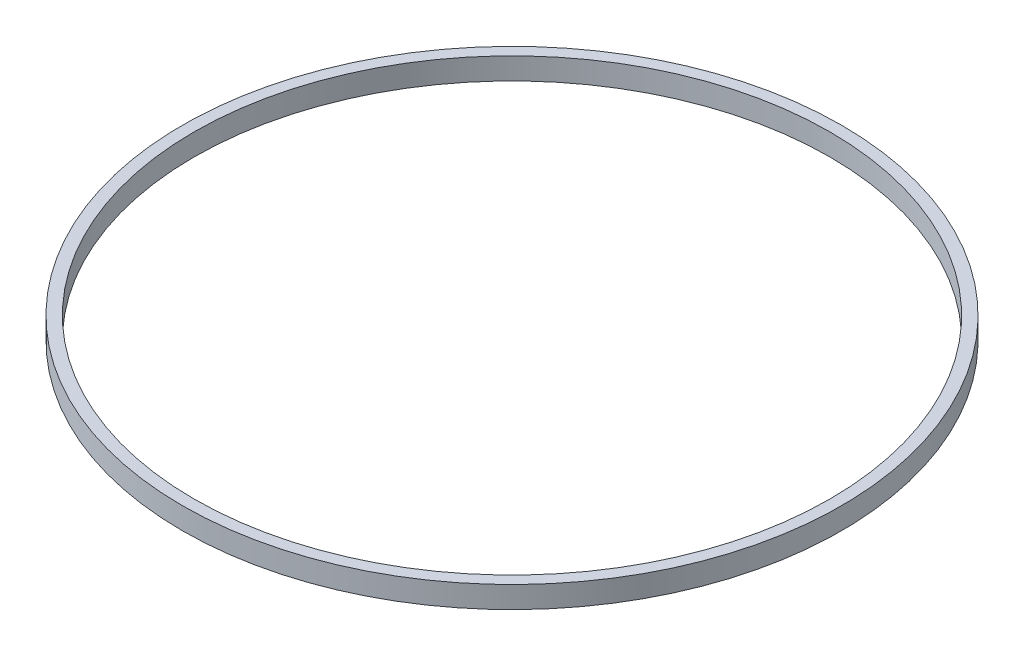
SolidWorks part; units mm, degrees
material "PE High Density"
ref_plane "Front Plane" through (0, 0, 0) normal (0, 0, 1) x (1, 0, 0)
ref_plane "Top Plane" through (0, 0, 0) normal (0, 1, 0) x (1, 0, 0)
ref_plane "Right Plane" through (0, 0, 0) normal (1, 0, 0) x (0, 0, -1)
ref_axis "X-Axis" through (-88.99, 0, 0) along (1, 0, 0)
ref_axis "Y-Axis" through (0, 55, 0) along (0, -1, 0)
ref_axis "Z-Axis" through (0, 0, -88.99) along (0, 0, 1)
sketch "Sketch1" plane through (0, 0, 0) normal (0, 1, 0) x (1, 0, 0)
  circle A0 centre (0, 0) radius 43.815
  dimension "D1" = 87.63
extrude "Extrude-Thin1" add sketch "Sketch1" along normal blind 2.9972 thin thin type one direction wall 1.6002
